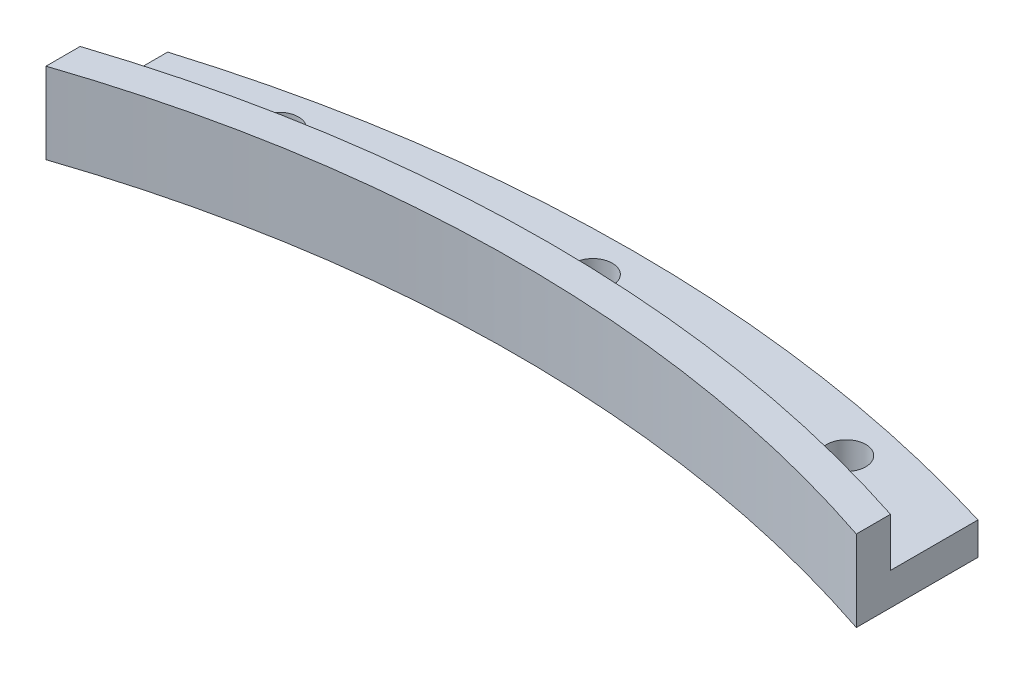
SolidWorks part; units mm, degrees
ref_plane "Спереди" through (0, 0, 0) normal (0, 0, 1) x (1, 0, 0)
ref_plane "Сверху" through (0, 0, 0) normal (0, 1, 0) x (1, 0, 0)
ref_plane "Справа" through (0, 0, 0) normal (1, 0, 0) x (0, 0, -1)
sketch "Эскиз1" plane through (0, 0, 0) normal (0, 1, 0) x (1, 0, 0)
  line L0 (-50, 5.4) -> (-50, 0)
  line L1 (0, 0) -> (0, 5.4)
  line L2 (-50, 0) -> (0, 0) construction
  line L3 (-50, 5.4) -> (0, 5.4) construction
  line L4 (-50, -2.1069) -> (-50, 0)
  line L5 (0, -2.1069) -> (0, 0)
  arc A0 (0, 5.4) -> (-50, 5.4) centre (-25, -76.3634) ccw
  arc A1 (0, 0) -> (-50, 0) centre (-25, -76.5196) ccw
  arc A2 (-50, -2.1069) -> (0, -2.1069) centre (-25, -76.5196) cw
  dimension "D1" = 80.5
  dimension "D2" = 85.5
  dimension "D5" = 2
  dimension "D3" = 50
  dimension "D4" = 5.4
extrude "Бобышка-Вытянуть1" add sketch "Эскиз1" along normal blind 2 contours A1 L1 A0 L0 region at (-25, 0, -5.2688)
extrude "Бобышка-Вытянуть2" add sketch "Эскиз1<3>" along normal blind 5 contours L4 A2 L5 A1 region at (-25, 0, -3.4767)
sketch "Эскиз1<3>" plane through (0, 0, 0) normal (0, 1, 0) x (1, 0, 0) same geometry as "Эскиз1"
sketch "Эскиз2" plane through (0, 0, 0) normal (0, -1, 0) x (1, 0, 0)
  line L0 (-50, -5.4) -> (-50, 2.1069) construction
  line L1 (0, 2.1069) -> (0, -5.4) construction
  line L2 (-42.5, -4.7708) -> (-7.5, -4.7708) construction
  line L3 (-25, -6.6366) -> (-25, -4.7708) construction
  arc A0 (-50, -5.4) -> (0, -5.4) centre (-25, 76.3634) ccw construction
  arc A1 (-50, -5.4) -> (0, -5.4) centre (-25, 76.3634) ccw construction
  arc A2 (-50, -2.7821) -> (0, -2.7821) centre (-25, 76.3634) ccw construction
  dimension "D1" = 2.5
  dimension "D2" = 35
hole_wizard "Отверстие с зазором M21" positions "Эскиз3" profile "Эскиз4" hole size "M2" standard "DIN" end condition up to next
sketch "Эскиз3" plane through (0, 0, 0) normal (0, -1, 0) x (-1, 0, 0)
  point P0 (42.5, 4.7708)
  point P3 (25, 6.6366)
  point P6 (7.5, 4.7708)
sketch "Эскиз4" plane through (-42.5, 0, -4.7708) normal (1, 0, 0) x (0, 0, -1)
  line L0 (0, 0) -> (0, 2)
  line L1 (0, 2) -> (1.2, 2)
  line L2 (1.2, 2) -> (1.2, 0)
  line L5 (1.2, 0) -> (0, 0)
  line L11 (0, -6.35) -> (0, 107.95) construction
  dimension "Диаметр сквозного отверстия" = 2.4
  dimension "Глубина сквозного отверстия" = 2
